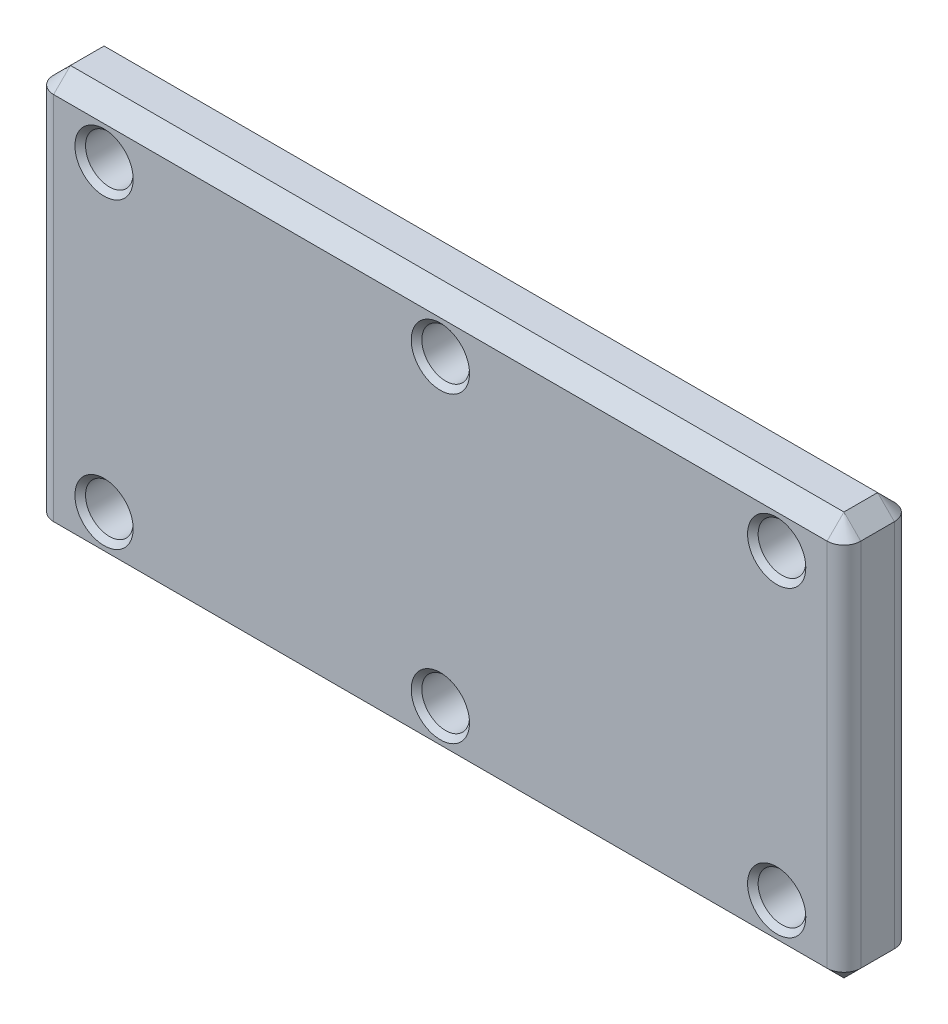
SolidWorks part; units mm, degrees
material "ABS"
ref_plane "Front Plane" through (0, 0, 0) normal (0, 0, 1) x (1, 0, 0)
ref_plane "Top Plane" through (0, 0, 0) normal (0, 1, 0) x (1, 0, 0)
ref_plane "Right Plane" through (0, 0, 0) normal (1, 0, 0) x (0, 0, -1)
ref_axis "X Axis" through (88.99, 0, 0) along (-1, 0, 0)
ref_axis "Y Axis" through (0, 55, 0) along (0, -1, 0)
ref_axis "Z Axis" through (0, 0, -88.99) along (0, 0, 1)
sketch "Sketch1" plane through (0, 0, 0) normal (0, 0, 1) x (1, 0, 0)
  line L1 (38.1, -19.05) -> (-38.1, -19.05)
  line L2 (38.1, -19.05) -> (38.1, 19.05)
  line L3 (38.1, 19.05) -> (-38.1, 19.05)
  line L4 (-38.1, -19.05) -> (-38.1, 19.05)
  line L5 (0, 19.05) -> (0, -19.05) construction
  line L6 (38.1, 0) -> (-38.1, 0) construction
  point P0 (0, 0)
  dimension "D1" = 76.2
  dimension "D2" = 38.1
extrude "Boss-Extrude1" add sketch "Sketch1" along normal mid plane 6.35
extrude "Boss-Extrude2" add sketch "Sketch1<2>" along normal mid plane 6.35
sketch "Sketch1<2>" plane through (0, 0, 0) normal (0, 0, 1) x (1, 0, 0) same geometry as "Sketch1"
sketch "Sketch8" plane through (0, 0, 0) normal (0, 1, 0) x (1, 0, 0)
  line L0 (-36.8427, 2.921) -> (-36.2505, 1.651) construction
  line L1 (-38.1, 3.175) -> (-33.02, 3.175)
  line L2 (-38.1, 3.175) -> (-38.1, 2.921)
  line L3 (-38.1, 2.921) -> (-33.02, 2.921) construction
  line L4 (-33.02, 3.175) -> (-33.02, 2.921)
  line L5 (-35.56, 2.921) -> (-35.56, 3.175) construction
  line L6 (-38.1, 3.048) -> (-33.02, 3.048) construction
  line L7 (-36.2505, 1.651) -> (-34.8695, 1.651) construction
  line L8 (-34.8695, 1.651) -> (-34.2773, 2.921) construction
  line L9 (-34.2773, 2.921) -> (-36.8427, 2.921) construction
  line L12 (-36.8507, 2.7016) -> (-36.4165, 1.7704)
  line L13 (-36.0721, 1.551) -> (-35.0479, 1.551)
  line L14 (-34.7035, 1.7704) -> (-34.2693, 2.7016)
  line L15 (-36.9333, 2.8787) -> (-36.3142, 1.551) construction
  line L16 (-34.8058, 1.551) -> (-34.1867, 2.8787) construction
  line L17 (-38.1, 2.921) -> (-37.1951, 2.921)
  line L18 (-33.9249, 2.921) -> (-33.02, 2.921)
  line L19 (-36.3142, 1.551) -> (-34.8058, 1.551) construction
  arc A0 (-34.2693, 2.7016) -> (-33.9249, 2.921) centre (-33.9249, 2.541) cw
  arc A1 (-35.0479, 1.551) -> (-34.7035, 1.7704) centre (-35.0479, 1.931) ccw
  arc A2 (-36.4165, 1.7704) -> (-36.0721, 1.551) centre (-36.0721, 1.931) ccw
  arc A3 (-36.8507, 2.7016) -> (-37.1951, 2.921) centre (-37.1951, 2.541) ccw
  point P6 (-35.56, 2.921)
  point P11 (-35.56, 1.651)
  point P20 (-34.167, 2.921)
  point P29 (-36.953, 2.921)
  point P48 (-35.56, 3.048)
  dimension "D6" = 0.1
  dimension "D7" = 0.38
  dimension "D1" = 50
  dimension "D2" = 1.27
  dimension "D3" = 2.5654
  dimension "D4" = 0.254
  dimension "D5" = 5.08
extrude "Cut-Extrude1" cut sketch "Sketch8" against normal mid plane 6.858 from offset 6.35 offset against normal yes
pattern_linear "LPattern1" count 15 spacing 5.08 along (1, 0, 0) count 2 spacing 12.7 along (0, 1, 0) of "Cut-Extrude1"
sketch "Sketch10" [suppressed] plane through (0, 0, -3.175) normal (0, 0, -1) x (-1, 0, 0)
  line L0 (-38.1, -19.05) -> (-38.1, 19.05) construction
  line L1 (-38.1, 9.779) -> (38.1, 9.779)
  line L2 (-38.1, 9.779) -> (-38.1, 2.921)
  line L3 (-38.1, 2.921) -> (38.1, 2.921)
  line L4 (38.1, 9.779) -> (38.1, 2.921)
  line L5 (0, 2.921) -> (0, 9.779) construction
  line L6 (-38.1, 6.35) -> (38.1, 6.35) construction
  line L7 (38.1, 19.05) -> (38.1, -19.05) construction
  line L8 (0, 2.921) -> (0, -2.921) construction
  line L9 (-38.1, -2.921) -> (38.1, -2.921)
  line L10 (-38.1, -2.921) -> (-38.1, -9.779)
  line L11 (-38.1, -9.779) -> (38.1, -9.779)
  line L12 (38.1, -2.921) -> (38.1, -9.779)
  line L13 (0, -9.779) -> (0, -2.921) construction
  line L14 (-38.1, -6.35) -> (38.1, -6.35) construction
  point P14 (0, 0)
  point P76 (0, 6.35)
  point P81 (0, -6.35)
  dimension "D1" = 6.858
  dimension "D2" = 12.7
extrude "Cut-Extrude2" [suppressed] cut sketch "Sketch10" against normal blind 0.254
sketch "Sketch2" plane through (0, 0, 0) normal (0, 0, 1) x (1, 0, 0)
  line L1 (31.75, -14.2875) -> (-31.75, -14.2875) construction
  line L2 (31.75, -14.2875) -> (31.75, 14.2875) construction
  line L3 (31.75, 14.2875) -> (-31.75, 14.2875) construction
  line L4 (-31.75, -14.2875) -> (-31.75, 14.2875) construction
  line L5 (0, 14.2875) -> (0, -14.2875) construction
  line L6 (31.75, 0) -> (-31.75, 0) construction
  point P0 (0, 0)
  dimension "D1" = 63.5
  dimension "D2" = 28.575
sketch "Sketch5" plane through (0, 0, 3.175) normal (0, 0, 1) x (1, 0, 0)
  point P0 (-31.75, 14.2875)
  point P3 (-31.75, -14.2875)
  point P6 (0, 14.2875)
  point P9 (0, -14.2875)
  point P12 (31.75, 14.2875)
  point P15 (31.75, -14.2875)
hole_wizard "M4 Clearance Hole1" positions "Sketch5" profile "Sketch4" hole size "M4" standard "ANSI Metric" end condition up to next
sketch "Sketch4" plane through (-31.75, 14.2875, 3.175) normal (1, 0, 0) x (0, -1, 0)
  line L0 (0, 0) -> (0, 6.35)
  line L1 (0, 6.35) -> (2.75, 6.35)
  line L2 (2.25, 5.85) -> (2.25, 0.5)
  line L3 (2.25, 0.5) -> (2.75, 0)
  line L5 (2.75, 0) -> (0, 0)
  line L6 (-2.25, 0.5) -> (-2.75, 0) construction
  line L7 (2.75, 6.35) -> (2.25, 5.85)
  line L8 (-2.75, 6.35) -> (-2.25, 5.85) construction
  line L11 (0, -6.35) -> (0, 107.95) construction
  dimension "Thru Hole Dia." = 4.5
  dimension "Thru Hole Depth" = 6.35
  dimension "Near C'Sink Dia." = 5.5
  dimension "Near C'Sink Angle" = 90
  dimension "Far C'Sink Dia." = 5.5
  dimension "Far C'Sink Angle" = 90
fillet "Fillet1" radius 1.5875 4 edges at (-38.1, -14.4145, -3.175) (-38.1, 0, 3.175) (38.1, 0, 3.175) (38.1, -14.4145, -3.175)
chamfer "Chamfer1" distance 1.5875 angle 45 16 edges at (-38.1, 19.05, 0) (-37.635, 19.05, 2.71) (-37.635, 19.05, -2.71) (0, 19.05, 3.175) (0, 19.05, -3.175) (37.635, 19.05, 2.71) (37.635, 19.05, -2.71) (38.1, 19.05, 0) (-38.1, -19.05, 0) (-37.635, -19.05, 2.71) (-37.635, -19.05, -2.71) (0, -19.05, 3.175) (0, -19.05, -3.175) (37.635, -19.05, 2.71) (37.635, -19.05, -2.71) (38.1, -19.05, 0)
chamfer "Chamfer2" distance 0.254 angle 45 12 edges at (36.9615, -9.779, -3.1102) (-36.9615, -9.779, -3.1102) (0, -9.779, -3.175) (36.9615, -2.921, -3.1102) (-36.9615, -2.921, -3.1102) (0, -2.921, -3.175) (36.9615, 2.921, -3.1102) (-36.9615, 2.921, -3.1102) (0, 2.921, -3.175) (36.9615, 9.779, -3.1102) (-36.9615, 9.779, -3.1102) (0, 9.779, -3.175)
chamfer "Chamfer3" [suppressed] distance 0.254 angle 45
